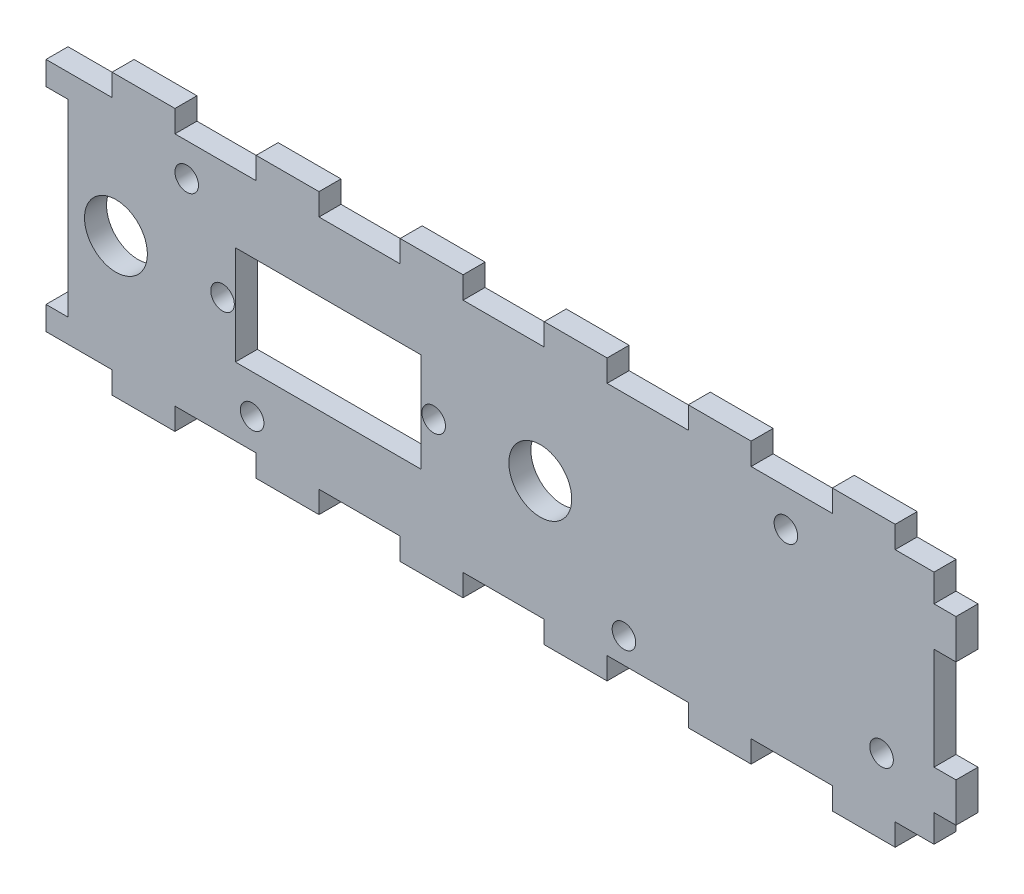
SolidWorks part; units mm, degrees
material "Фанера"
ref_plane "Front Plane" through (0, 0, 0) normal (0, 0, 1) x (1, 0, 0)
ref_plane "Top Plane" through (0, 0, 0) normal (0, 1, 0) x (1, 0, 0)
ref_plane "Right Plane" through (0, 0, 0) normal (1, 0, 0) x (0, 0, -1)
sketch "Эскиз1" plane through (0, 0, 0) normal (0, 0, 1) x (1, 0, 0)
  line L5 (0, -19.2753) -> (0, 20.3224) construction
  line L6 (-55.1, 15) -> (-49.49, 15)
  line L11 (-55.1, 12) -> (-55.1, 11.5)
  line L12 (-55.1, -15) -> (-49.49, -15)
  line L29 (55.1, 15) -> (55.1, 11.5)
  line L54 (-55.1, 15) -> (55.1, -15) construction
  line L60 (-55.1, -15) -> (55.1, 15) construction
  line L61 (-64.8201, 0) -> (75.1963, 0) construction
  line L62 (55.1, -5) -> (55.1, -6.5)
  line L67 (55.1, 5) -> (55.1, -5)
  line L68 (55.1, 6.5) -> (55.1, 5)
  line L69 (50.16, -15) -> (55.1, -15)
  line L71 (42.16, -15) -> (42.16, -17.8)
  line L72 (42.16, -17.8) -> (50.16, -17.8)
  line L74 (46.16, -15) -> (50.16, -17.8) construction
  line L75 (42.16, -17.8) -> (46.16, -15) construction
  line L76 (50.16, -15) -> (50.16, -17.8)
  line L77 (23.83, -17.8) -> (31.83, -17.8)
  line L78 (23.83, -15) -> (23.83, -17.8)
  line L79 (31.83, -15) -> (31.83, -17.8)
  line L80 (5.5, -17.8) -> (13.5, -17.8)
  line L81 (5.5, -15) -> (5.5, -17.8)
  line L82 (13.5, -15) -> (13.5, -17.8)
  line L83 (-12.83, -17.8) -> (-4.83, -17.8)
  line L84 (-12.83, -15) -> (-12.83, -17.8)
  line L85 (-4.83, -15) -> (-4.83, -17.8)
  line L86 (-31.16, -17.8) -> (-23.16, -17.8)
  line L87 (-31.16, -15) -> (-31.16, -17.8)
  line L88 (-23.16, -15) -> (-23.16, -17.8)
  line L89 (-49.49, -17.8) -> (-41.49, -17.8)
  line L90 (-49.49, -15) -> (-49.49, -17.8)
  line L91 (-41.49, -15) -> (-41.49, -17.8)
  line L92 (-41.49, -15) -> (-31.16, -15)
  line L93 (-23.16, -15) -> (-12.83, -15)
  line L94 (-4.83, -15) -> (5.5, -15)
  line L95 (13.5, -15) -> (23.83, -15)
  line L96 (31.83, -15) -> (42.16, -15)
  line L97 (50.16, 15) -> (50.16, 17.8)
  line L98 (42.16, 17.8) -> (50.16, 17.8)
  line L99 (42.16, 15) -> (42.16, 17.8)
  line L100 (31.83, 15) -> (31.83, 17.8)
  line L101 (23.83, 17.8) -> (31.83, 17.8)
  line L102 (23.83, 15) -> (23.83, 17.8)
  line L103 (13.5, 15) -> (13.5, 17.8)
  line L104 (5.5, 17.8) -> (13.5, 17.8)
  line L105 (5.5, 15) -> (5.5, 17.8)
  line L106 (-4.83, 15) -> (-4.83, 17.8)
  line L107 (-12.83, 17.8) -> (-4.83, 17.8)
  line L108 (-12.83, 15) -> (-12.83, 17.8)
  line L109 (-23.16, 15) -> (-23.16, 17.8)
  line L110 (-31.16, 17.8) -> (-23.16, 17.8)
  line L111 (-31.16, 15) -> (-31.16, 17.8)
  line L112 (-41.49, 15) -> (-41.49, 17.8)
  line L113 (-49.49, 15) -> (-49.49, 17.8)
  line L114 (-49.49, 17.8) -> (-41.49, 17.8)
  line L115 (-41.49, 15) -> (-31.16, 15)
  line L116 (-23.16, 15) -> (-12.83, 15)
  line L117 (-4.83, 15) -> (5.5, 15)
  line L118 (13.5, 15) -> (23.83, 15)
  line L119 (31.83, 15) -> (42.16, 15)
  line L120 (50.16, 15) -> (55.1, 15)
  line L124 (-55.1, -5) -> (-55.1, -6.5)
  line L125 (55.1, 11.5) -> (57.9, 11.5)
  line L127 (55.1, 6.5) -> (57.9, 6.5)
  line L128 (57.9, 11.5) -> (57.9, 6.5)
  line L129 (55.1, 9) -> (57.9, 6.5) construction
  line L130 (55.1, 9) -> (57.9, 11.5) construction
  line L131 (-55.1, 5) -> (-55.1, -5)
  line L132 (55.1, -6.5) -> (57.9, -6.5)
  line L133 (57.9, -11.5) -> (57.9, -6.5)
  line L134 (55.1, -11.5) -> (57.9, -11.5)
  line L135 (55.1, -11.5) -> (55.1, -15)
  line L142 (-55.1, 6.5) -> (-55.1, 5)
  line L143 (-55.1, -11.5) -> (-55.1, -12)
  line L144 (-55.1, -11.5) -> (-55.1, -6.5)
  line L145 (-55.1, 6.5) -> (-55.1, 11.5)
  line L146 (-55.1, -15) -> (-57.9, -15)
  line L147 (-57.9, -15) -> (-57.9, -12)
  line L148 (-57.9, -12) -> (-55.1, -12)
  line L149 (-57.9, 12) -> (-55.1, 12)
  line L150 (-55.1, 15) -> (-57.9, 15)
  line L151 (-57.9, 15) -> (-57.9, 12)
  circle A2 centre (5, 0) radius 4
  circle A3 centre (-49, 0) radius 4
  point P0 (0, 0)
  point P10 (57.6, 0)
  point P11 (55.1, 9)
  point P17 (46.16, -15)
  dimension "D11" = 8
  dimension "D12" = 50.1
  dimension "D13" = 54
  dimension "D1" = 30
  dimension "D2" = 110.2
  dimension "D3" = 5
  dimension "D4" = 6
  dimension "D5" = 2.8
  dimension "D6" = 4.94
  dimension "D8" = 4
  dimension "D9" = 2.8
  dimension "D10" = 6
  dimension "D7" = 8
  dimension "D14" = 2.5
  dimension "D15" = 3
  dimension "D16" = 2.8
extrude "Бобышка-Вытянуть1" add sketch "Эскиз1" along normal mid plane 2.8
sketch "Эскиз2" plane through (0, 0, -1.4) normal (0, 0, -1) x (-1, 0, 0)
  line L0 (10.2, 6.3) -> (33.8, 6.3) construction
  line L1 (10.2, 6.3) -> (33.8, 6.3)
  line L2 (10.2, 6.3) -> (10.2, -6.3) construction
  line L3 (10.2, 6.3) -> (10.2, -6.3)
  line L4 (10.2, -6.3) -> (33.8, -6.3) construction
  line L5 (33.8, 6.3) -> (33.8, -6.3) construction
  line L6 (10.2, -6.3) -> (33.8, -6.3)
  line L7 (33.8, 6.3) -> (33.8, -6.3)
  line L60 (-55.1, -15) -> (-50.16, -15)
  line L61 (-50.16, -15) -> (-50.16, -17.8)
  line L62 (-50.16, -17.8) -> (-42.16, -17.8)
  line L63 (-42.16, -17.8) -> (-42.16, -15)
  line L64 (-42.16, -15) -> (-31.83, -15)
  line L65 (-31.83, -15) -> (-31.83, -17.8)
  line L66 (-31.83, -17.8) -> (-23.83, -17.8)
  line L67 (-23.83, -17.8) -> (-23.83, -15)
  line L68 (-23.83, -15) -> (-13.5, -15)
  line L69 (-13.5, -15) -> (-13.5, -17.8)
  line L70 (-13.5, -17.8) -> (-5.5, -17.8)
  line L71 (-5.5, -17.8) -> (-5.5, -15)
  line L72 (-5.5, -15) -> (4.83, -15)
  line L73 (4.83, -15) -> (4.83, -17.8)
  line L74 (4.83, -17.8) -> (12.83, -17.8)
  line L75 (12.83, -17.8) -> (12.83, -15)
  line L76 (12.83, -15) -> (23.16, -15)
  line L77 (23.16, -15) -> (23.16, -17.8)
  line L78 (23.16, -17.8) -> (31.16, -17.8)
  line L79 (31.16, -17.8) -> (31.16, -15)
  line L80 (31.16, -15) -> (41.49, -15)
  line L81 (41.49, -15) -> (41.49, -17.8)
  line L82 (41.49, -17.8) -> (49.49, -17.8)
  line L83 (49.49, -17.8) -> (49.49, -15)
  line L84 (49.49, -15) -> (57.9, -15)
  line L85 (55.1, -12) -> (55.1, 12)
  line L86 (-55.1, -11.5) -> (-55.1, -15)
  line L87 (-55.1, -11.5) -> (-55.1, -15)
  line L88 (57.9, -15) -> (57.9, -12)
  line L89 (57.9, -15) -> (57.9, -12)
  line L90 (57.9, 15) -> (49.49, 15)
  line L91 (49.49, 15) -> (49.49, 17.8)
  line L92 (49.49, 17.8) -> (41.49, 17.8)
  line L93 (41.49, 17.8) -> (41.49, 15)
  line L94 (41.49, 15) -> (31.16, 15)
  line L95 (31.16, 15) -> (31.16, 17.8)
  line L96 (31.16, 17.8) -> (23.16, 17.8)
  line L97 (23.16, 17.8) -> (23.16, 15)
  line L98 (23.16, 15) -> (12.83, 15)
  line L99 (12.83, 15) -> (12.83, 17.8)
  line L100 (12.83, 17.8) -> (4.83, 17.8)
  line L101 (4.83, 17.8) -> (4.83, 15)
  line L102 (4.83, 15) -> (-5.5, 15)
  line L103 (-5.5, 15) -> (-5.5, 17.8)
  line L104 (-5.5, 17.8) -> (-13.5, 17.8)
  line L105 (-13.5, 17.8) -> (-13.5, 15)
  line L106 (-13.5, 15) -> (-23.83, 15)
  line L107 (-23.83, 15) -> (-23.83, 17.8)
  line L108 (-23.83, 17.8) -> (-31.83, 17.8)
  line L109 (-31.83, 17.8) -> (-31.83, 15)
  line L110 (-31.83, 15) -> (-42.16, 15)
  line L111 (-42.16, 15) -> (-42.16, 17.8)
  line L112 (-42.16, 17.8) -> (-50.16, 17.8)
  line L113 (-50.16, 17.8) -> (-50.16, 15)
  line L114 (-50.16, 15) -> (-55.1, 15)
  line L115 (-55.1, 15) -> (-55.1, 11.5)
  line L116 (-55.1, 6.5) -> (-55.1, -6.5)
  line L118 (57.9, -12) -> (55.1, -12)
  line L120 (-55.1, -15) -> (-50.16, -15)
  line L121 (-50.16, -15) -> (-50.16, -17.8)
  line L122 (-50.16, -17.8) -> (-42.16, -17.8)
  line L123 (-42.16, -17.8) -> (-42.16, -15)
  line L124 (-42.16, -15) -> (-31.83, -15)
  line L125 (-31.83, -15) -> (-31.83, -17.8)
  line L126 (-31.83, -17.8) -> (-23.83, -17.8)
  line L127 (-23.83, -17.8) -> (-23.83, -15)
  line L128 (-23.83, -15) -> (-13.5, -15)
  line L129 (-13.5, -15) -> (-13.5, -17.8)
  line L130 (-13.5, -17.8) -> (-5.5, -17.8)
  line L131 (-5.5, -17.8) -> (-5.5, -15)
  line L132 (-5.5, -15) -> (4.83, -15)
  line L133 (4.83, -15) -> (4.83, -17.8)
  line L134 (4.83, -17.8) -> (12.83, -17.8)
  line L135 (12.83, -17.8) -> (12.83, -15)
  line L136 (12.83, -15) -> (23.16, -15)
  line L137 (23.16, -15) -> (23.16, -17.8)
  line L138 (23.16, -17.8) -> (31.16, -17.8)
  line L139 (31.16, -17.8) -> (31.16, -15)
  line L140 (31.16, -15) -> (41.49, -15)
  line L141 (41.49, -15) -> (41.49, -17.8)
  line L142 (41.49, -17.8) -> (49.49, -17.8)
  line L143 (49.49, -17.8) -> (49.49, -15)
  line L144 (49.49, -15) -> (57.9, -15)
  line L145 (55.1, -12) -> (55.1, 12)
  line L150 (57.9, 15) -> (49.49, 15)
  line L151 (49.49, 15) -> (49.49, 17.8)
  line L152 (49.49, 17.8) -> (41.49, 17.8)
  line L153 (41.49, 17.8) -> (41.49, 15)
  line L154 (41.49, 15) -> (31.16, 15)
  line L155 (31.16, 15) -> (31.16, 17.8)
  line L156 (31.16, 17.8) -> (23.16, 17.8)
  line L157 (23.16, 17.8) -> (23.16, 15)
  line L158 (23.16, 15) -> (12.83, 15)
  line L159 (12.83, 15) -> (12.83, 17.8)
  line L160 (12.83, 17.8) -> (4.83, 17.8)
  line L161 (4.83, 17.8) -> (4.83, 15)
  line L162 (4.83, 15) -> (-5.5, 15)
  line L163 (-5.5, 15) -> (-5.5, 17.8)
  line L164 (-5.5, 17.8) -> (-13.5, 17.8)
  line L165 (-13.5, 17.8) -> (-13.5, 15)
  line L166 (-13.5, 15) -> (-23.83, 15)
  line L167 (-23.83, 15) -> (-23.83, 17.8)
  line L168 (-23.83, 17.8) -> (-31.83, 17.8)
  line L169 (-31.83, 17.8) -> (-31.83, 15)
  line L170 (-31.83, 15) -> (-42.16, 15)
  line L171 (-42.16, 15) -> (-42.16, 17.8)
  line L172 (-42.16, 17.8) -> (-50.16, 17.8)
  line L173 (-50.16, 17.8) -> (-50.16, 15)
  line L174 (-50.16, 15) -> (-55.1, 15)
  line L175 (-55.1, 15) -> (-55.1, 11.5)
  line L176 (-55.1, 6.5) -> (-55.1, -6.5)
  line L192 (57.9, -12) -> (55.1, -12)
  line L193 (55.1, 12) -> (57.9, 12)
  line L194 (55.1, 12) -> (57.9, 12)
  line L195 (57.9, 12) -> (57.9, 15)
  line L196 (57.9, 12) -> (57.9, 15)
  line L206 (-55.1, 11.5) -> (-57.9, 11.5)
  line L207 (-55.1, 11.5) -> (-57.9, 11.5)
  line L208 (-57.9, 11.5) -> (-57.9, 6.5)
  line L209 (-57.9, 11.5) -> (-57.9, 6.5)
  line L210 (-57.9, 6.5) -> (-55.1, 6.5)
  line L211 (-57.9, 6.5) -> (-55.1, 6.5)
  line L212 (-55.1, -6.5) -> (-57.9, -6.5)
  line L213 (-55.1, -6.5) -> (-57.9, -6.5)
  line L214 (-57.9, -6.5) -> (-57.9, -11.5)
  line L215 (-57.9, -6.5) -> (-57.9, -11.5)
  line L216 (-57.9, -11.5) -> (-55.1, -11.5)
  line L217 (-57.9, -11.5) -> (-55.1, -11.5)
  circle A0 centre (35.435, 0) radius 1.5 construction
  circle A1 centre (8.565, 0) radius 1.5 construction
  circle A2 centre (35.435, 0) radius 1.5
  circle A3 centre (8.565, 0) radius 1.5
  dimension "D1" = 0
extrude "Вырез-Вытянуть1" cut sketch "Эскиз2" against normal through all both and the other way through all contours L7 L1 L3 L6 | A3 | A2 region at (-22, 0, -1.4) region at (-35.435, 0, -1.4) region at (-8.565, 0, -1.4)
sketch "Эскиз3" plane through (0, 0, -1.4) normal (0, 0, -1) x (-1, 0, 0)
  circle A0 centre (31.6679, -11.2285) radius 1.5 construction
  circle A1 centre (-48.4294, -8.3) radius 1.5 construction
  circle A2 centre (-15.6482, -11.7437) radius 1.5 construction
  circle A3 centre (39.9924, 10.8146) radius 1.5 construction
  circle A4 centre (-36.2531, 10.2844) radius 1.5 construction
  circle A5 centre (31.6679, -11.2285) radius 1.5
  circle A6 centre (-48.4294, -8.3) radius 1.5
  circle A7 centre (-15.6482, -11.7437) radius 1.5
  circle A8 centre (39.9924, 10.8146) radius 1.5
  circle A9 centre (-36.2531, 10.2844) radius 1.5
extrude "Вырез-Вытянуть2" cut sketch "Эскиз3" against normal through all both and the other way through all
